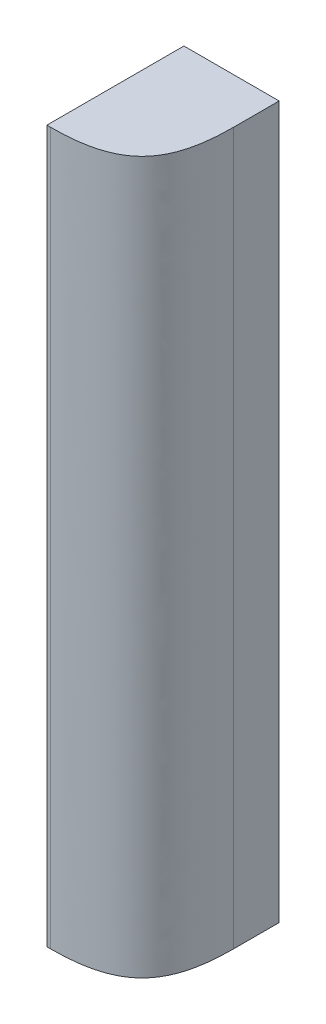
SolidWorks part; units mm, degrees
ref_plane "Front Plane" through (0, 0, 0) normal (0, 0, 1) x (1, 0, 0)
ref_plane "Top Plane" through (0, 0, 0) normal (0, 1, 0) x (1, 0, 0)
ref_plane "Right Plane" through (0, 0, 0) normal (1, 0, 0) x (0, 0, -1)
sketch "Sketch1" plane through (0, 0, 0) normal (0, 1, 0) x (1, 0, 0)
  line L1 (0, 0) -> (25, 0)
  line L2 (0, 0) -> (0, 36)
  line L3 (0, 36) -> (25, 36)
  line L4 (25, 0) -> (25, 36)
  dimension "D1" = 36
  dimension "D2" = 25
extrude "Boss-Extrude1" add sketch "Sketch1" along normal blind 186.9
fillet "Fillet1" radius 24 1 edges at (25, 93.45, 0) conic rho 0.55
sketch "Sketch2" plane through (0, 0, 0) normal (-1, 0, 0) x (0, 0, 1)
  line L0 (-24, 0) -> (0, 0) construction
  line L1 (-6.2, 83.2) -> (-1.2, 83.2)
  line L2 (-6.2, 83.2) -> (-6.2, 73.2)
  line L3 (-6.2, 73.2) -> (-1.2, 73.2)
  line L4 (-1.2, 83.2) -> (-1.2, 73.2)
  line L5 (0, 186.9) -> (0, 0) construction
  dimension "D1" = 73.2
  dimension "D2" = 1.2
  dimension "D3" = 5
  dimension "D4" = 10
extrude "Cut-Extrude1" cut sketch "Sketch2" against normal blind 4
sketch "Sketch3" plane through (0, 0, 0) normal (-1, 0, 0) x (0, 0, 1)
  line L1 (-14, 33.2) -> (-6, 33.2)
  line L2 (-14, 33.2) -> (-14, 28)
  line L3 (-14, 28) -> (-6, 28)
  line L4 (-6, 33.2) -> (-6, 28)
  line L5 (-36, 0) -> (0, 0) construction
  line L6 (0, 186.9) -> (0, 0) construction
  line L8 (-22, 33.2) -> (-30, 33.2)
  line L9 (-22, 33.2) -> (-22, 28)
  line L10 (-22, 28) -> (-30, 28)
  line L11 (-30, 33.2) -> (-30, 28)
  line L12 (-6, 61.2) -> (-14, 61.2)
  line L13 (-6, 61.2) -> (-6, 66.8)
  line L14 (-6, 66.8) -> (-14, 66.8)
  line L15 (-14, 61.2) -> (-14, 66.8)
  line L16 (-22, 66.8) -> (-30, 66.8)
  line L17 (-22, 66.8) -> (-22, 61.2)
  line L18 (-22, 61.2) -> (-30, 61.2)
  line L19 (-30, 66.8) -> (-30, 61.2)
  dimension "D1" = 28
  dimension "D2" = 6
  dimension "D3" = 8
  dimension "D4" = 5.2
  dimension "D5" = 8
  dimension "D6" = 8
  dimension "D7" = 28
  dimension "D8" = 5.6
  dimension "D9" = 8
  dimension "D10" = 6
  dimension "D11" = 8
  dimension "D12" = 5.6
  dimension "D13" = 8
extrude "Cut-Extrude2" cut sketch "Sketch3" against normal blind 10
